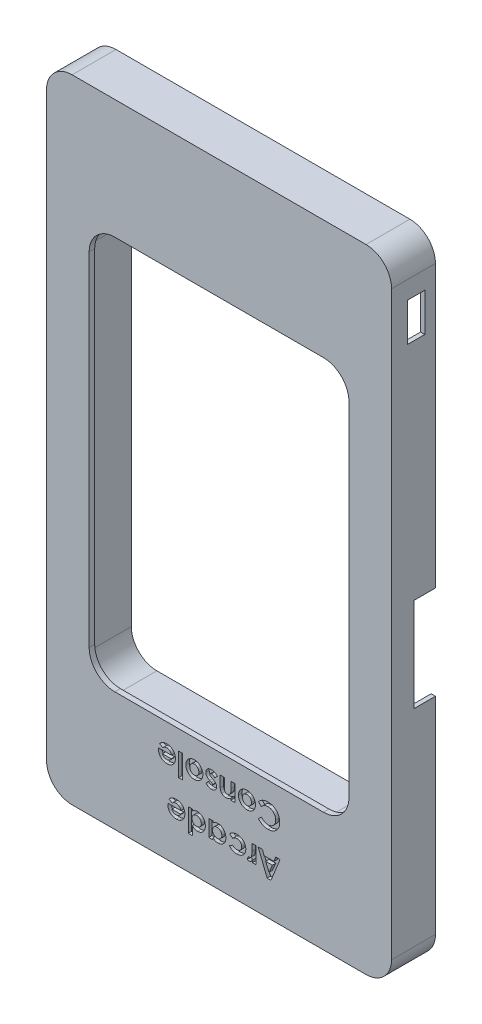
SolidWorks part; units mm, degrees
ref_plane "Ebene vorne" through (0, 0, 0) normal (1, 0, 0) x (0, 1, 0)
ref_plane "Ebene oben" through (0, 0, 0) normal (0, 0, 1) x (0, 1, 0)
ref_plane "Ebene rechts" through (0, 0, 0) normal (0, 1, 0) x (-1, 0, 0)
sketch "DiplayCase" plane through (0, 0, 0) normal (0, 0, 1) x (0, 1, 0)
  line L1 (-46.22, -30.5) -> (46.22, -30.5)
  line L2 (-46.22, -30.5) -> (-46.22, 30.5)
  line L3 (-46.22, 30.5) -> (46.22, 30.5)
  line L4 (46.22, -30.5) -> (46.22, 30.5)
  line L5 (-46.22, -30.5) -> (46.22, 30.5) construction
  line L6 (-46.22, 30.5) -> (46.22, -30.5) construction
  line L7 (-74.22, -40.5) -> (74.22, -40.5)
  line L8 (-74.22, -40.5) -> (-74.22, 40.5)
  line L9 (-74.22, 40.5) -> (74.22, 40.5)
  line L10 (74.22, -40.5) -> (74.22, 40.5)
  line L11 (-74.22, -40.5) -> (74.22, 40.5) construction
  line L12 (-74.22, 40.5) -> (74.22, -40.5) construction
  point P0 (0, 0)
  point P6 (0, 0)
  dimension "D1" = 61
  dimension "D2" = 92.44
  dimension "D3" = 10
  dimension "D4" = 28
  dimension "D5" = 148.44
  dimension "D6" = 81
extrude "UpperCase" add sketch "DiplayCase" along normal blind 10.3
fillet "Verrundung1" radius 6 4 edges at (30.5, 46.22, 5.15) (-30.5, 46.22, 5.15) (30.5, -46.22, 5.15) (-30.5, -46.22, 5.15)
sketch "Skizze2" plane through (0, 0, 0) normal (0, 0, -1) x (1, 0, 0)
  line L1 (-30.9, -47.32) -> (30.9, -47.32)
  line L2 (-30.9, -47.32) -> (-30.9, 47.32)
  line L3 (-30.9, 47.32) -> (30.9, 47.32)
  line L4 (30.9, -47.32) -> (30.9, 47.32)
  line L5 (-30.9, -47.32) -> (30.9, 47.32) construction
  line L6 (-30.9, 47.32) -> (30.9, -47.32) construction
  point P0 (0, 0)
  dimension "D1" = 61.8
  dimension "D2" = 94.64
extrude "Schnitt-Linear austragen1" cut sketch "Skizze2" against normal blind 9
fillet "Verrundung2" radius 6 4 edges at (40.5, -74.22, 5.15) (-40.5, -74.22, 5.15) (40.5, 74.22, 5.15) (-40.5, 74.22, 5.15)
fillet "Verrundung3" radius 6 4 edges at (-30.9, 47.32, 4.5) (30.9, 47.32, 4.5) (30.9, -47.32, 4.5) (-30.9, -47.32, 4.5)
shell "Wandung2" thickness 1 removed face at (0, 0, 0)
sketch "Skizze8" plane through (0, 0, 10.3) normal (0, 0, 1) x (0, -1, 0)
  line L0 (46.22, 0) -> (74.22, 0) construction
  line L1 (46.22, -24.5) -> (46.22, 24.5) construction
  line L2 (74.22, -34.5) -> (74.22, 34.5) construction
  line L3 (60.9348, 18.5) -> (60.9348, -18.5) construction
  text T0 "Arcade \r\nConsole" font "Century Gothic" height in points 20
  point P10 (60.9348, 0)
extrude "Text_ArcadeConsole" cut sketch "Skizze8" against normal blind 0.8
sketch "Skizze11" plane through (0, 47.32, 0) normal (0, -1, 0) x (1, 0, 0)
  line L1 (-10.85, -8.17) -> (10.85, -8.17)
  line L2 (-10.85, -8.17) -> (-10.85, 8.17)
  line L3 (-10.85, 8.17) -> (10.85, 8.17)
  line L4 (10.85, -8.17) -> (10.85, 8.17)
  line L5 (-10.85, -8.17) -> (10.85, 8.17) construction
  line L6 (-10.85, 8.17) -> (10.85, -8.17) construction
  point P0 (0, 0)
  dimension "D1" = 21.7
  dimension "D2" = 16.34
extrude "Hole_DisplayCables" cut sketch "Skizze11" against normal blind 1
sketch "Skizze12" plane through (0, 0, 9.3) normal (0, 0, -1) x (1, 0, 0)
  line L1 (-31.5, -66) -> (31.5, -66) construction
  line L2 (-31.5, -66) -> (-31.5, 66) construction
  line L3 (-31.5, 66) -> (31.5, 66) construction
  line L4 (31.5, -66) -> (31.5, 66) construction
  line L5 (-31.5, -66) -> (31.5, 66) construction
  line L6 (-31.5, 66) -> (31.5, -66) construction
  circle A2 centre (34, 68) radius 2.5
  circle A3 centre (34, 68) radius 1.25
  circle A4 centre (-34, 68) radius 2.5
  circle A5 centre (-34, 68) radius 1.25
  circle A6 centre (34, -68) radius 2.5
  circle A7 centre (34, -68) radius 1.25
  circle A8 centre (-34, -68) radius 2.5
  circle A9 centre (-34, -68) radius 1.25
  circle A12 centre (-34, -44.85) radius 2.5
  circle A13 centre (-34, -44.85) radius 1.25
  circle A14 centre (34, -44.85) radius 2.5
  circle A15 centre (34, -44.85) radius 1.25
  point P0 (0, 0)
  dimension "D3" = 5
  dimension "D4" = 2.5
  dimension "D6" = 2.5
  dimension "D7" = 5
  dimension "D8" = 2.5
  dimension "D11" = 5
  dimension "D12" = 2.5
  dimension "D15" = 5
  dimension "D16" = 2.5
  dimension "D1" = 63
  dimension "D2" = 132
  dimension "D5" = 2
  dimension "D9" = 2.5
  dimension "D10" = 2
  dimension "D13" = 2.5
  dimension "D14" = 2
  dimension "D17" = 112.85
  dimension "D18" = 112.85
extrude "Aufsatz-Linear austragen4" add sketch "Skizze12" along normal blind 4 contours A4 | A5 | A3 | A2 | A13 | A12 | A14 | A15
sketch "Skizze16" plane through (40.5, 0, 0) normal (1, 0, 0) x (0, 1, 0)
  line L0 (-68.22, 0) -> (68.22, 0) construction
  line L2 (2.22, 0) -> (-19.78, 0)
  line L3 (2.22, 0) -> (2.22, 5)
  line L4 (2.22, 5) -> (-19.78, 5)
  line L5 (-19.78, 0) -> (-19.78, 5)
  dimension "D1" = 66
  dimension "D2" = 22
  dimension "D3" = 5
extrude "Schnitt-Linear austragen3" cut sketch "Skizze16" against normal blind 11
sketch "Skizze18" plane through (-40.5, 0, 0) normal (-1, 0, 0) x (0, -1, 0)
  line L0 (-66.4183, 3.7385) -> (-35.1656, 3.7385) construction
  line L2 (-63.9183, 3.7385) -> (-54.9783, 3.7385) construction
  line L3 (-63.9183, 5.8685) -> (-54.9783, 5.8685)
  line L4 (-63.9183, 1.6085) -> (-54.9783, 1.6085)
  arc A0 (-63.9183, 5.8685) -> (-63.9183, 1.6085) centre (-63.9183, 3.7385) ccw
  arc A1 (-54.9783, 1.6085) -> (-54.9783, 5.8685) centre (-54.9783, 3.7385) ccw
  point P6 (-59.4483, 3.7385)
  dimension "D1" = 8.94
  dimension "D2" = 4.26
  dimension "D3" = 2.5
  dimension "D4" = 4.15
extrude "Schnitt-Linear austragen4" cut sketch "Skizze18" against normal blind 1
extrude "Aufsatz-Linear austragen5" add sketch "Skizze12<6>" along normal blind 2
sketch "Skizze12<6>" plane through (0, 0, 9.3) normal (0, 0, -1) x (1, 0, 0) same geometry as "Skizze12"
sketch "Skizze19" plane through (40.5, 0, 0) normal (1, 0, 0) x (0, 1, 0)
  line L0 (68.22, 0) -> (68.22, 10.3) construction
  line L1 (55.02, 2.5) -> (64.02, 2.5)
  line L2 (55.02, 2.5) -> (55.02, 6.5)
  line L3 (55.02, 6.5) -> (64.02, 6.5)
  line L4 (64.02, 2.5) -> (64.02, 6.5)
  line L5 (55.02, 2.5) -> (64.02, 6.5) construction
  line L6 (55.02, 6.5) -> (64.02, 2.5) construction
  line L8 (2.22, 0) -> (68.22, 0) construction
  point P0 (59.52, 4.5)
  dimension "D1" = 9
  dimension "D2" = 4
  dimension "D3" = 4.2
  dimension "D4" = 2.5
extrude "Schnitt-Linear austragen5" cut sketch "Skizze19" against normal blind 5
